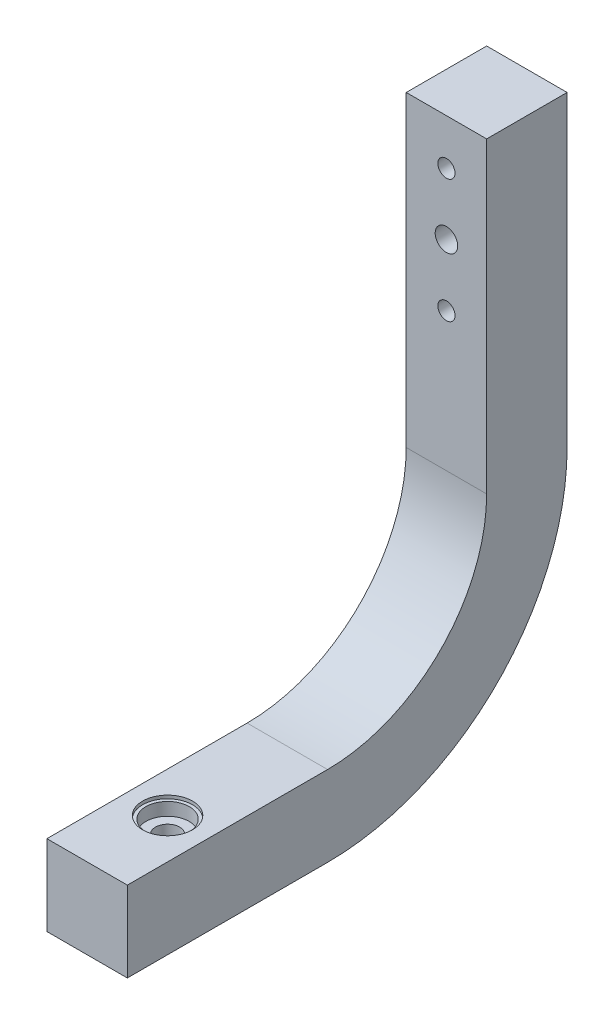
SolidWorks part; units mm, degrees
ref_plane "Front Plane" through (0, 0, 0) normal (0, 0, 1) x (1, 0, 0)
ref_plane "Top Plane" through (0, 0, 0) normal (0, 1, 0) x (1, 0, 0)
ref_plane "Right Plane" through (0, 0, 0) normal (1, 0, 0) x (0, 0, -1)
ref_axis "Z" through (0, 0, 86.1) along (0, 0, -1)
sketch "Sketch1" plane through (0, 0, 0) normal (1, 0, 0) x (0, 0, -1)
  line L0 (-15, 20) -> (0, 20)
  line L1 (0, 20) -> (0, -37.3333)
  line L2 (0, -32) -> (-50, -82) construction
  line L3 (-44.6667, -82) -> (-67, -82)
  line L4 (-67, -82) -> (-67, -67) construction
  line L5 (-67, -67) -> (-44.6667, -67)
  line L6 (-56.2132, -67) -> (-15, -25.7868) construction
  line L7 (-15, -37.3333) -> (-15, 20)
  line L8 (-35.6066, -46.3934) -> (-25, -57) construction
  line L9 (-44.6667, -67) -> (-56.2132, -67) construction
  line L10 (-67, -67) -> (-82, -67)
  line L11 (-67, -67) -> (-67, -82) construction
  line L12 (-67, -82) -> (-82, -82)
  line L13 (-82, -67) -> (-82, -82)
  line L14 (-15, -25.7868) -> (-15, -37.3333) construction
  line L15 (0, -37.3333) -> (0, -32) construction
  line L16 (-50, -82) -> (-44.6667, -82) construction
  arc A0 (-44.6667, -67) -> (-15, -37.3333) centre (-44.6667, -37.3333) ccw
  arc A1 (-44.6667, -82) -> (0, -37.3333) centre (-44.6667, -37.3333) ccw
  dimension "D1" = 15
  dimension "D2" = 67
  dimension "D3" = 82
  dimension "D4" = 20
  dimension "D5" = 135
  dimension "D6" = 50
  dimension "D7" = 15
  dimension "D8" = 22.3333
extrude "Boss-Extrude1" add sketch "Sketch1" along normal blind 7.5 and the other way blind 7.5
sketch "Sketch3" plane through (0, -67, 0) normal (0, 1, 0) x (1, 0, 0)
  line L0 (-8.25, 0) -> (8.25, 0) construction
  line L1 (0, -45.1) -> (0, 45.1) construction
  circle A0 centre (0, -67) radius 2.25
  dimension "D2" = 4.5
  dimension "D1" = 67
extrude "Cut-Extrude1" cut sketch "Sketch3" against normal through all
sketch "Sketch4" plane through (0, 0, 15) normal (0, 0, 1) x (1, 0, 0)
  line L0 (0, -11.5) -> (0, 11.5) construction
  circle A0 centre (0, 0) radius 2.1
  circle A1 centre (0, 11.5) radius 1.6
  circle A2 centre (0, -11.5) radius 1.6
  dimension "D1" = 4.2
  dimension "D3" = 3.2
  dimension "D2" = 23
extrude "Cut-Extrude2" cut sketch "Sketch4" against normal through all both and the other way through all
ref_axis "Axis1" through (0, -52.3642, 67) along (0, 1, 0)
sketch "Sketch5" plane through (0, 0, 0) normal (1, 0, 0) x (0, 0, -1)
  line L0 (-62.95, -79) -> (-62.95, -81.4)
  line L1 (-62.95, -81.4) -> (-62.35, -81.4)
  line L2 (-62.35, -81.4) -> (-62.35, -82)
  line L3 (-62.35, -82) -> (-67, -82)
  line L4 (-67, -82) -> (-67, -79)
  line L5 (-67, -79) -> (-62.95, -79)
  line L6 (-67, -74.5) -> (-67, -90.6731) construction
  line L7 (-67, -74.5) -> (-82, -74.5) construction
  line L8 (-67, -70) -> (-62.95, -70)
  line L9 (-67, -67) -> (-67, -70)
  line L10 (-62.35, -67) -> (-67, -67)
  line L11 (-62.35, -67.6) -> (-62.35, -67)
  line L12 (-62.95, -67.6) -> (-62.35, -67.6)
  line L13 (-62.95, -70) -> (-62.95, -67.6)
  line L16 (-67, -67) -> (-67, -36.7401) construction
  line L17 (-82, -67) -> (-82, -82) construction
  line L18 (-67, -67) -> (-44.6667, -67) construction
  point P15 (-84.9322, -76.3954)
  point P16 (-90.3733, -70.8282)
  dimension "D2" = 4.65
  dimension "D3" = 3
  dimension "D4" = 8.1
revolve "Cut-Revolve1" cut sketch "Sketch5" angle 360 about axis through (0, -52.3642, 67) along (0, 1, 0)
equation "\"rbracket-width\"= \"L2Thickness\""
equation "\"D1@Boss-Extrude1\"=\"rbracket-width\"/2"
equation "\"D2@Boss-Extrude1\"=\"rbracket-width\"/2"
equation "\"EyeCaptureRadius\"= ( \"EyeDiameter\" + \"EyeClearance\" ) / 2"
equation "\"rbracket_planetocenterline_dist\"= \"BasePlaneDistance\""
equation "\"D2@Sketch1\"=\"rbracket_planetocenterline_dist\""
equation "\"EyeDiameter\" = 100"
equation "\"BasePlaneDistance\" = \"EyeDiameter\"/2+\"L2Thickness\"+\"EyeClearance\""
equation "\"EyeClearance\" = 2"
equation "\"D1@Sketch1\"=\"rbracket-width\""
equation "\"D3@Sketch1\"=(\"EyeDiameter\"+\"EyeClearance\"+\"EyeClearance\")/2 + \"L2Thickness\" + \"rbracket-width\""
equation "\"D6@Sketch1\"=\"EyeDiameter\"/2"
equation "\"D7@Sketch1\"=\"rbracket-width\""
equation "\"D1@Sketch3\"=\"BasePlaneDistance\""
equation "\"L2Thickness\" = 15"
equation "\"D8@Sketch1\"=\"rbracket_planetocenterline_dist\"/3"
equation "\"BearingFlangeOD\"= 7.5"
equation "\"BearingFlangeThickness\"= 0.75"
equation "\"BearingHousingID\"=4.5"
equation "\"BearingDepth\"= 6"
equation "\"PrinterFilamentThickness\"= 0.1"
equation "\"ApplyPrinterOffsets\"= 1"
equation "\"L2_ID\" = 20"
equation "\"vx\" = 0"
equation "\"vy\" = 0"
equation "\"vz\" = 100"
equation "\"parametric_end\" = 1"
equation "\"Rw_3_xx\" = -(\"vz\")/sqr((\"vx\")^2 + (\"vz\")^2)"
equation "\"Rw_3_xy\" = 0"
equation "\"Rw_3_xz\" = (\"vx\")/sqr((\"vx\")^2 + (\"vz\")^2)"
equation "\"Rw_3_zx\" = (\"vx\")/sqr((\"vx\")^2 + (\"vy\")^2 + (\"vz\")^2)"
equation "\"Rw_3_zy\" = (\"vy\")/sqr((\"vx\")^2 + (\"vy\")^2 + (\"vz\")^2)"
equation "\"Rw_3_zz\" = (\"vz\")/sqr((\"vx\")^2 + (\"vy\")^2 + (\"vz\")^2)"
equation "\"Rw_3_yx\" = (\"vx\")*(\"vy\")/sqr((\"vx\")^4 + (\"vx\")^2*(\"vy\")^2 + 2*(\"vx\")^2*(\"vz\")^2 + (\"vy\")^2*(\"vz\")^2 + (\"vz\")^4)"
equation "\"Rw_3_yy\" = -sqr((\"vx\")^2 + (\"vz\")^2)/sqr((\"vx\")^2 + (\"vy\")^2 + (\"vz\")^2)"
equation "\"Rw_3_yz\" = (\"vy\")*(\"vz\")/sqr((\"vx\")^4 + (\"vx\")^2*(\"vy\")^2 + 2*(\"vx\")^2*(\"vz\")^2 + (\"vy\")^2*(\"vz\")^2 + (\"vz\")^4)"
equation "\"O2Targx\" = -\"BasePlaneDistance\"*(\"vx\")*(\"vy\")/sqr((\"vx\")^4 + (\"vx\")^2*(\"vy\")^2 + 2*(\"vx\")^2*(\"vz\")^2 + (\"vy\")^2*(\"vz\")^2 + (\"vz\")^4)"
equation "\"O2Targy\" = \"BasePlaneDistance\"*sqr((\"vx\")^2 + (\"vz\")^2)/sqr((\"vx\")^2 + (\"vy\")^2 + (\"vz\")^2)"
equation "\"O2Targz\" = -\"BasePlaneDistance\"*(\"vy\")*(\"vz\")/sqr((\"vx\")^4 + (\"vx\")^2*(\"vy\")^2 + 2*(\"vx\")^2*(\"vz\")^2 + (\"vy\")^2*(\"vz\")^2 + (\"vz\")^4)"
equation "\"O2Targx_0\" = -(\"BasePlaneDistance\")*sqr((\"vx\")^2 + (\"vz\")^2)/sqr((\"vx\")^2 + (\"vy\")^2 + (\"vz\")^2)"
equation "\"O2Targy_0\" = -(\"BasePlaneDistance\")*(\"vy\")*(\"vz\")/sqr((\"vx\")^4 + (\"vx\")^2*(\"vy\")^2 + 2*(\"vx\")^2*(\"vz\")^2 + (\"vy\")^2*(\"vz\")^2 + (\"vz\")^4)"
equation "\"O2Targz_0\" = (\"BasePlaneDistance\")*(\"vx\")*(\"vy\")/sqr((\"vx\")^4 + (\"vx\")^2*(\"vy\")^2 + 2*(\"vx\")^2*(\"vz\")^2 + (\"vy\")^2*(\"vz\")^2 + (\"vz\")^4) + (\"BasePlaneDistance\")"
equation "\"theta2_s1\" = arcsin(((\"BasePlaneDistance\") - (\"O2Targz_0\"))/(\"BasePlaneDistance\")) + pi"
equation "\"theta2_s2\" = -arcsin(((\"BasePlaneDistance\") - (\"O2Targz_0\"))/(\"BasePlaneDistance\"))"
equation "\"theta1_s1\" = arcsin((\"O2Targy_0\")/((\"BasePlaneDistance\")*cos((\"Theta2\")))) + pi"
equation "\"theta1_s2\" = -arcsin((\"O2Targy_0\")/((\"BasePlaneDistance\")*cos((\"Theta2\"))))"
equation "\"theta1_s3\" = -arccos(-(\"O2Targx_0\")/((\"BasePlaneDistance\")*cos((\"Theta2\")))) + 2*pi"
equation "\"theta1_s4\" = arccos(-(\"O2Targx_0\")/((\"BasePlaneDistance\")*cos((\"Theta2\"))))"
equation "\"Theta1\" = \"theta1_s2\" 'so far, theta1_s1 and theta1_s4 have agreed, and they agree with the sw constraint solver"
equation "\"Theta2\" = \"theta2_s2\""
equation "\"o2_x\" = -(\"BasePlaneDistance\")*cos((\"Theta1\"))*cos((\"Theta2\"))"
equation "\"o2_y\" = -(\"BasePlaneDistance\")*sin((\"Theta1\"))*cos((\"Theta2\"))"
equation "\"o2_z\" = (\"BasePlaneDistance\")*(sin((\"Theta2\")) + 1)"
equation "\"o1_x\" = (\"BasePlaneDistance\")*sin((\"Theta1\"))"
equation "\"o1_y\" = -(\"BasePlaneDistance\")*cos((\"Theta1\"))"
equation "\"o1_z\" = (\"BasePlaneDistance\")"
equation "\"Actuator1_Theta\" = atn(\"vx\"/\"vz\") 'ik solution for the single link joint"
equation "\"Actuator2_Theta\" = \"Theta1\"  'ik solution for the double link joint"
equation "\"MotorBaseThickness\" = 3 "
equation "\"BaseThickness\" = 3 "
equation "\"EncoderToMagnetAirgap\" = 1 'Encoder to magnet airgap"
equation "\"EncoderHeight\" = 1.192  'Height of the encoder"
equation "\"MagnetThickness\" = 0.5  'Magnet thickness"
equation "\"pcb_thickness\" = 1.6  'Thickness of the PCB"
equation "\"pcb_outer_diameter\" = 32 'the OD of the pcb"
equation "\"shaft_diameter\" = 4"
equation "\"D2@Sketch3\"=\"shaft_diameter\"*1.125"
equation "\"D2@Sketch5\"=\"ApplyPrinterOffsets\"*\"PrinterFilamentThickness\"/2+4.6"
equation "\"D4@Sketch5\"=\"ApplyPrinterOffsets\"*\"PrinterFilamentThickness\"+8"
